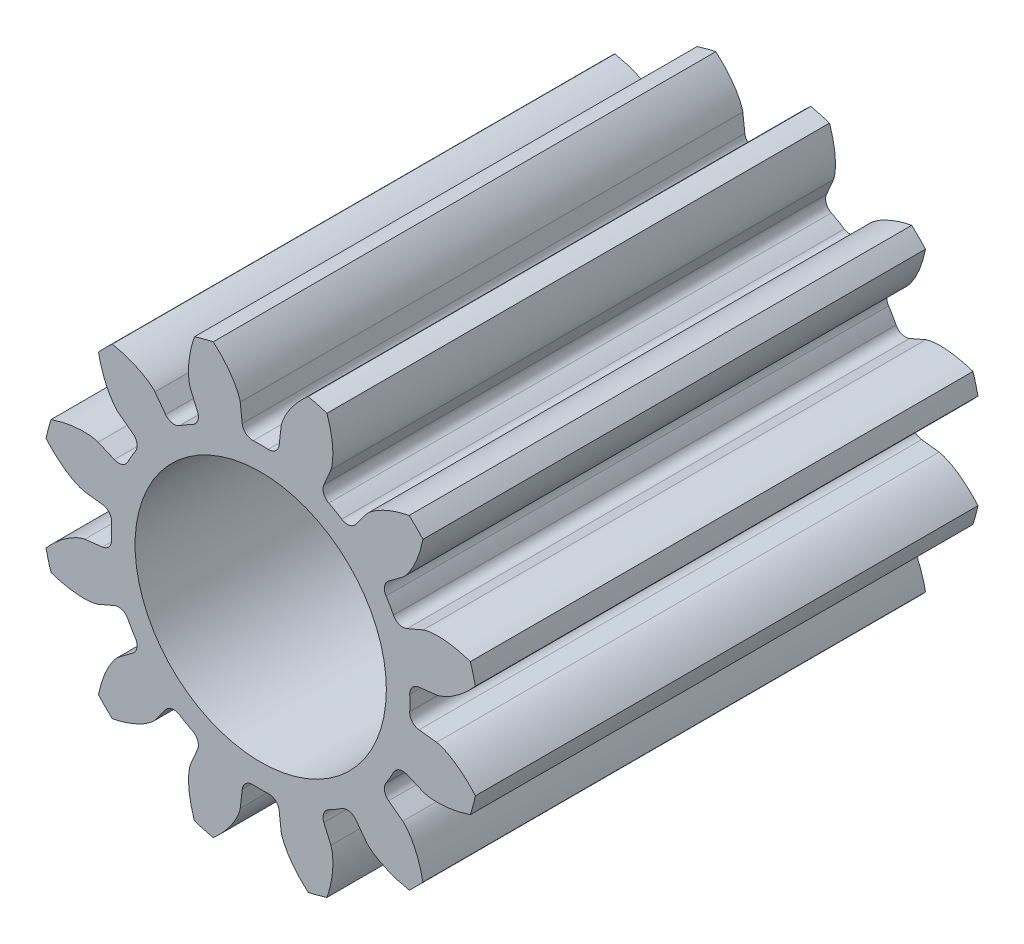
SolidWorks part; units mm, degrees
ref_plane "Front Plane" through (0, 0, 0) normal (0, 0, 1) x (1, 0, 0)
ref_plane "Top Plane" through (0, 0, 0) normal (0, 1, 0) x (1, 0, 0)
ref_plane "Right Plane" through (0, 0, 0) normal (1, 0, 0) x (0, 0, -1)
sketch "Sketch1" plane through (0, 0, 0) normal (0, 0, 1) x (1, 0, 0)
  line L0 (0, 0) -> (0, 4.7625) construction
  line L1 (-1.5306, 5.3196) -> (1.5306, 4.2054) construction
  circle A0 centre (0, 0) radius 3.7703 construction
  circle A1 centre (0, 0) radius 5.5562 construction
  circle A2 centre (0, 0) radius 4.7625 construction
  circle A3 centre (0, 0) radius 4.4753 construction
  point P8 (406.4, 0)
  point P13 (152.4, 0)
  dimension "OD | Outside Diameter" = 11.1125
  dimension "Root Diameter" = 7.5406
  dimension "Gear Pitch Diameter" = 9.525
  dimension "Base Diameter" = 8.9506
  dimension "Pressure Angle" = 20
  dimension "Number of Teeth" = 304.8
  dimension "Gear Pitch | Diametral Pitch" = 812.8
sketch "Sketch2" plane through (0, 0, 0) normal (1, 0, 0) x (0, 0, -1)
  line L0 (-6.35, 0) -> (6.35, 0) construction
  point P2 (-0.7938, 0)
  point P5 (1.9844, 0)
  point P6 (0.7938, 0)
  dimension "Length" = 12.7
  dimension "D1" = 5.5562
  dimension "D2" = 8.3344
  dimension "D3" = 5.5562
sketch "Sketch3" plane through (0, 0, 0) normal (0, 0, 1) x (1, 0, 0)
  circle A0 centre (0, 0) radius 5.5562
  circle A1 centre (0, 0) radius 5.5562 construction
extrude "Boss-Extrude1" add sketch "Sketch3" against normal up to vertex (6.35 mm away) and the other way up to vertex (6.35 mm away) up to point (0, 0, -6.35) other way up to point (0, 0, 6.35)
sketch "Sketch4" plane through (0, 0, 0) normal (0, 0, 1) x (1, 0, 0)
  line L0 (0, 0) -> (3.745, 0.4364) construction
  line L2 (0, 0) -> (3.745, -0.4364) construction
  line L4 (3.745, 0.4364) -> (4.4452, 0.5179)
  line L5 (4.4452, -0.5179) -> (3.745, -0.4364)
  arc A0 (3.745, 0.4364) -> (3.745, -0.4364) centre (0, 0) cw
  arc A3 (5.4254, 1.1987) -> (5.4254, -1.1987) centre (0, 0) cw
  circle A4 centre (0, 0) radius 5.5562 construction
  spline S0 degree 4 poles (4.4452, 0.5179) (4.447, 0.5182) (4.452, 0.5189) (4.4613, 0.5207) (4.4765, 0.524) (4.4957, 0.5289) (4.5203, 0.5361) (4.5491, 0.5456) (4.5805, 0.5571) (4.6143, 0.5707) (4.6477, 0.5853) (4.6807, 0.6008) (4.7133, 0.6171) (4.7525, 0.6378) (4.799, 0.6639) (4.8525, 0.6964) (4.9122, 0.7355) (4.9721, 0.7778) (5.03, 0.8214) (5.0874, 0.8676) (5.1422, 0.9139) (5.1978, 0.9642) (5.2486, 1.0117) (5.304, 1.0674) (5.3484, 1.113) (5.4053, 1.1756) (5.4385, 1.2134) (5.4767, 1.2584) (5.4934, 1.2789) (5.5037, 1.2914) knots 0 0 0 0 0 0.005377 0.015084 0.028532 0.04661 0.064855 0.092111 0.119476 0.146842 0.174209 0.201575 0.228941 0.256307 0.307035 0.361767 0.4165 0.471232 0.525964 0.580697 0.635429 0.690161 0.744894 0.799626 0.854358 0.909091 0.954545 1 1 1 1 1 construction
  spline S1 degree 4 poles (4.4452, 0.5179) (4.447, 0.5182) (4.452, 0.5189) (4.4613, 0.5207) (4.4765, 0.524) (4.4957, 0.5289) (4.5203, 0.5361) (4.5491, 0.5456) (4.5805, 0.5571) (4.6143, 0.5707) (4.6477, 0.5853) (4.6807, 0.6008) (4.7133, 0.6171) (4.7525, 0.6378) (4.799, 0.6639) (4.8525, 0.6964) (4.9122, 0.7355) (4.9721, 0.7778) (5.03, 0.8214) (5.0874, 0.8676) (5.1422, 0.9139) (5.1978, 0.9642) (5.2486, 1.0117) (5.304, 1.0674) (5.3484, 1.113) (5.393, 1.1621) (5.4145, 1.1862) (5.4254, 1.1987) knots 0 0 0 0 0 0.005377 0.015084 0.028532 0.04661 0.064855 0.092111 0.119476 0.146842 0.174209 0.201575 0.228941 0.256307 0.307035 0.361767 0.4165 0.471232 0.525964 0.580697 0.635429 0.690161 0.744894 0.799626 0.854358 0.909091 0.909091 0.909091 0.909091 0.909091
  spline S2 degree 4 poles (4.4452, -0.5179) (4.447, -0.5182) (4.452, -0.5189) (4.4613, -0.5207) (4.4765, -0.524) (4.4957, -0.5289) (4.5203, -0.5361) (4.5491, -0.5456) (4.5805, -0.5571) (4.6143, -0.5707) (4.6477, -0.5853) (4.6807, -0.6008) (4.7133, -0.6171) (4.7525, -0.6378) (4.799, -0.6639) (4.8525, -0.6964) (4.9122, -0.7355) (4.9721, -0.7778) (5.03, -0.8214) (5.0874, -0.8676) (5.1422, -0.9139) (5.1978, -0.9642) (5.2486, -1.0117) (5.304, -1.0674) (5.3484, -1.113) (5.4053, -1.1756) (5.4385, -1.2134) (5.4767, -1.2584) (5.4934, -1.2789) (5.5037, -1.2914) knots 0 0 0 0 0 0.005377 0.015084 0.028532 0.04661 0.064855 0.092111 0.119476 0.146842 0.174209 0.201575 0.228941 0.256307 0.307035 0.361767 0.4165 0.471232 0.525964 0.580697 0.635429 0.690161 0.744894 0.799626 0.854358 0.909091 0.954545 1 1 1 1 1 construction
  spline S3 degree 4 poles (4.4452, -0.5179) (4.447, -0.5182) (4.452, -0.5189) (4.4613, -0.5207) (4.4765, -0.524) (4.4957, -0.5289) (4.5203, -0.5361) (4.5491, -0.5456) (4.5805, -0.5571) (4.6143, -0.5707) (4.6477, -0.5853) (4.6807, -0.6008) (4.7133, -0.6171) (4.7525, -0.6378) (4.799, -0.6639) (4.8525, -0.6964) (4.9122, -0.7355) (4.9721, -0.7778) (5.03, -0.8214) (5.0874, -0.8676) (5.1422, -0.9139) (5.1978, -0.9642) (5.2486, -1.0117) (5.304, -1.0674) (5.3484, -1.113) (5.393, -1.1621) (5.4145, -1.1862) (5.4254, -1.1987) knots 0 0 0 0 0 0.005377 0.015084 0.028532 0.04661 0.064855 0.092111 0.119476 0.146842 0.174209 0.201575 0.228941 0.256307 0.307035 0.361767 0.4165 0.471232 0.525964 0.580697 0.635429 0.690161 0.744894 0.799626 0.854358 0.909091 0.909091 0.909091 0.909091 0.909091
  dimension "D1" = 7.5406
extrude "Cut-Extrude1" cut sketch "Sketch4" against normal through all both and the other way through all
fillet "Fillet1" radius 0.2663 2 edges at (3.745, -0.4364, 0) (3.745, 0.4364, 0)
pattern_circular "CirPattern1" count 12 over 360 about axis through (0, 0, 6.35) along (0, 0, -1) of "Cut-Extrude1", "Fillet1"
sketch "Sketch5" plane through (0, 0, 6.35) normal (0, 0, 1) x (1, 0, 0)
  point P0 (0, 0)
hole_wizard "1/4 (0.2500) Dowel Hole1" positions "Sketch5" profile "Sketch6" hole size "1/4" standard "ANSI Inch" end condition through all
sketch "Sketch6" plane through (0, 0, 6.35) normal (1, 0, 0) x (0, -1, 0)
  line L0 (0, 0) -> (0, 12.7)
  line L1 (0, 12.7) -> (3.175, 12.7)
  line L2 (3.175, 12.7) -> (3.175, 0)
  line L5 (3.175, 0) -> (0, 0)
  line L11 (0, -6.35) -> (0, 107.95) construction
  dimension "Thru Hole Dia." = 6.35
  dimension "Thru Hole Depth" = 12.7
equation "\"Root Diameter@Sketch1\"=\"Root Diameter\""
equation "\"OD | Outside Diameter@Sketch1\"=\"Outside Diameter\""
equation "\"D1@CirPattern1\"=\"Number of Teeth\""
equation "\"Diametral Pitch\"=32"
equation "\"Number of Teeth\"=12"
equation "\"Pressure Angle\"=20"
equation "\"Pitch Diameter\"= \"Number of Teeth\" / \"Diametral Pitch\""
equation "\"Base Diameter\"= \"Pitch Diameter\" * cos ( \"Pressure Angle\" )"
equation "\"Outside Diameter\"= ( \"Number of Teeth\" + 2 ) / \"Diametral Pitch\""
equation "\"Dedendum\"= 1.25 / \"Diametral Pitch\""
equation "\"Root Diameter\"= \"Pitch Diameter\" - ( 2 * \"Dedendum\" )"
equation "\"Pitch Angle\"= 360deg / \"Number of Teeth\""
equation "\"Alpha\"= sqr ( \"Pitch Diameter\" ^ 2 - \"Base Diameter\" ^ 2 ) / \"Base Diameter\" * 180 / PI - \"Pressure Angle\""
equation "\"Beta\"= ( \"Pitch Angle\" / 4 - \"Alpha\" )"
equation "\"Phi\"= sqr ( ( \"Outside Diameter\" / 2 ) ^ 2 - ( \"Base Diameter\" / 2 ) ^ 2 ) / ( \"Base Diameter\" / 2 )"
equation "\"Addendum\"= 1 / \"Diametral Pitch\""
equation "\"WorkingDepth\"= 2 / \"Diametral Pitch\""
equation "\"WholeDepth\"= 2.25 / \"Diametral Pitch\""
equation "\"Clearance\"= 0.25 / \"Diametral Pitch\""
equation "\"ToothThickness\"= ( pi * 2 ) / \"Diametral Pitch\""
equation "\"CircularPitch\"= pi / \"Diametral Pitch\""
equation "\"Number of Teeth@Sketch1\"=\"Number of Teeth\""
equation "\"Gear Pitch | Diametral Pitch@Sketch1\"=\"Diametral Pitch\""
equation "\"Pressure Angle@Sketch1\"=\"Pressure Angle\""
equation "\"Gear Pitch Diameter@Sketch1\"=\"Pitch Diameter\""
equation "\"Base Diameter@Sketch1\"=\"Base Diameter\""
equation "\"Fillet\"= \"Clearance\" * cos ( \"Pressure Angle\" ) * tan ( ( 90 + \"Pressure Angle\" ) / 2 )"
equation "\"D1@Fillet1\"=\"Fillet\""
equation "\"D1@Sketch4\"=if( \"Base Diameter\">\"Root Diameter\",\"Root Diameter\",\"Base Diameter\"-.00001)"
equation "\"D1@Sketch2\"=\"OD | Outside Diameter@Sketch1\"*2*0.5*0.5"
equation "\"D2@Sketch2\"=\"D1@Sketch2\"*1.5"
equation "\"D3@Sketch2\"=\"D1@Sketch2\""
equation "\"Length\"= .5"
equation "\"Length@Sketch2\"= \"Length\""
